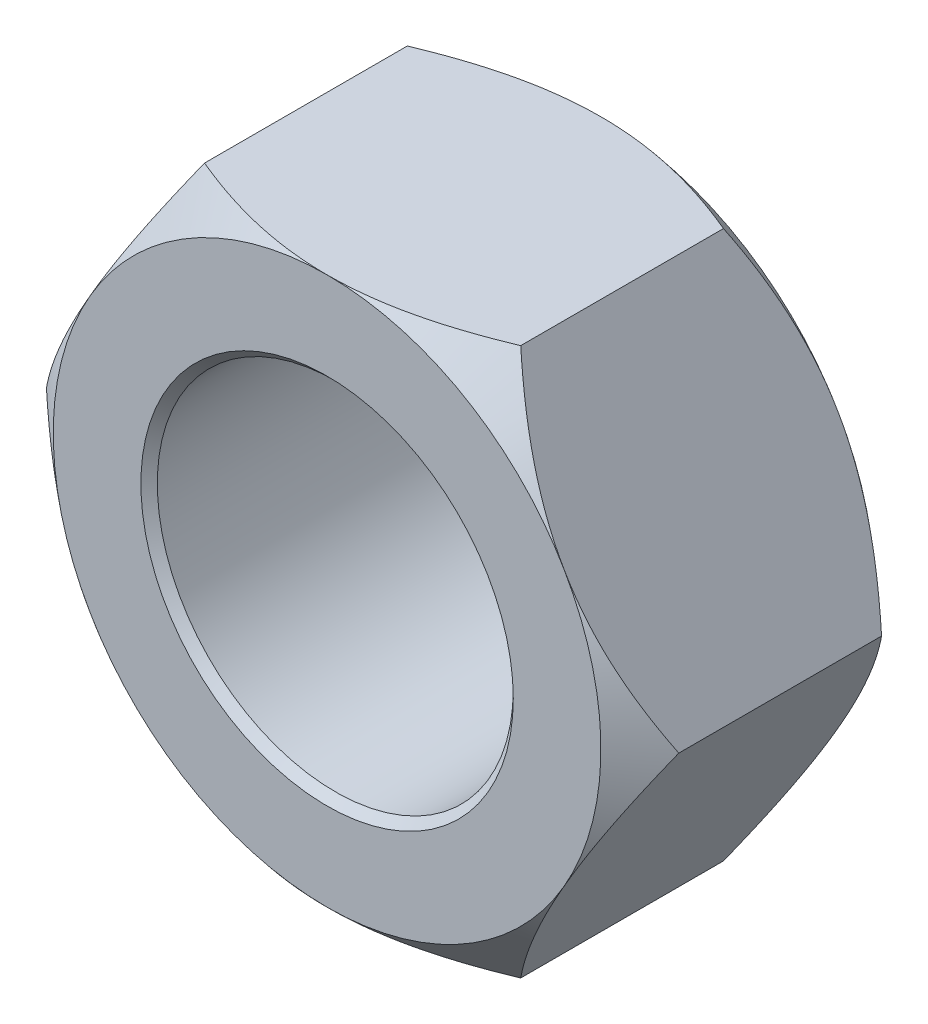
SolidWorks part; units mm, degrees
ref_plane "Front Plane" through (0, 0, 0) normal (0, 0, 1) x (1, 0, 0)
ref_plane "Top Plane" through (0, 0, 0) normal (0, 1, 0) x (1, 0, 0)
ref_plane "Right Plane" through (0, 0, 0) normal (1, 0, 0) x (0, 0, -1)
sketch "Sketch1" plane through (0, 0, 0) normal (0, 0, 1) x (1, 0, 0)
  line L1 (-11.547, 0) -> (-5.7735, -10)
  line L2 (-5.7735, -10) -> (5.7735, -10)
  line L3 (5.7735, -10) -> (11.547, 0)
  line L4 (11.547, 0) -> (5.7735, 10)
  line L5 (5.7735, 10) -> (-5.7735, 10)
  line L6 (-5.7735, 10) -> (-11.547, 0)
  circle A0 centre (0, 0) radius 10 construction
  circle A1 centre (0, 0) radius 6.5
  point P10 (0, 0)
  dimension "D1" = 13
  dimension "D2" = 20
extrude "Boss-Extrude1" add sketch "Sketch1" along normal blind 10
sketch "Sketch2" plane through (0, 0, 10) normal (0, 0, 1) x (1, 0, 0)
  line L0 (-5.7735, 10) -> (-11.547, 0) construction
  circle A0 centre (0, 0) radius 10
extrude "Cut-Extrude1" cut sketch "Sketch2" against normal blind 3 draft 50 flip side to cut
ref_plane "Plane1" through (0, 0, 5) normal (0, 0, -1) x (-1, 0, 0)
mirror "Mirror1" about plane through (0, 0, 5) normal (0, 0, -1) of "Cut-Extrude1"
ref_axis "Axis1" through (0, 0, 10) along (0, 0, -1)
chamfer "Chamfer1" distance 0.3 angle 45 2 edges at (6.5, 0, 0) (6.5, 0, 10)
